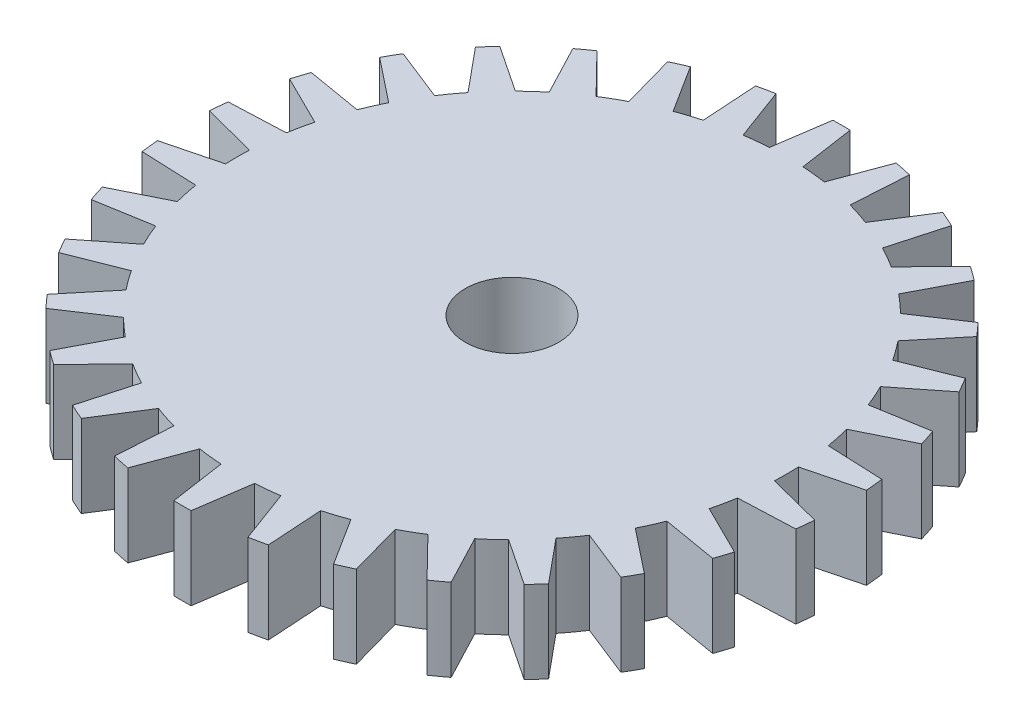
SolidWorks part; units mm, degrees
ref_plane "Front Plane" through (0, 0, 0) normal (0, 0, 1) x (1, 0, 0)
ref_plane "Top Plane" through (0, 0, 0) normal (0, 1, 0) x (1, 0, 0)
ref_plane "Right Plane" through (0, 0, 0) normal (1, 0, 0) x (0, 0, -1)
sketch "Sketch1" plane through (0, 0, 0) normal (0, 1, 0) x (1, 0, 0)
  line L0 (0, 0) -> (0, 12) construction
  line L1 (0, 0) -> (-0.3141, 11.9959) construction
  line L2 (0, 0) -> (-0.6105, 9.9813) construction
  line L3 (0, 0) -> (-1.0453, 9.9452) construction
  line L4 (-0.3141, 11.9959) -> (-0.6105, 9.9813)
  line L5 (0.3141, 11.9959) -> (0.6105, 9.9813)
  line L6 (2.1868, 11.7991) -> (1.4781, 9.8902)
  line L7 (2.8013, 11.6684) -> (2.6724, 9.6363)
  line L8 (4.5922, 11.0866) -> (3.5021, 9.3667)
  line L9 (5.1661, 10.831) -> (4.6175, 8.8701)
  line L10 (6.7969, 9.8895) -> (5.373, 8.4339)
  line L11 (7.3051, 9.5202) -> (6.3608, 7.7162)
  line L12 (8.7045, 8.2603) -> (7.0091, 7.1325)
  line L13 (9.1249, 7.7934) -> (7.8261, 6.2251)
  line L14 (10.2317, 6.27) -> (8.3389, 5.5194)
  line L15 (10.5458, 5.7259) -> (8.9493, 4.462)
  line L16 (11.3117, 4.0057) -> (9.3042, 3.665)
  line L17 (11.5058, 3.4082) -> (9.6815, 2.5038)
  line L18 (11.8973, 1.5663) -> (9.8629, 1.6505)
  line L19 (11.963, 0.9415) -> (9.9905, 0.4362)
  line L20 (11.963, -0.9415) -> (9.9905, -0.4362)
  line L21 (11.8973, -1.5663) -> (9.8629, -1.6505)
  line L22 (11.5058, -3.4082) -> (9.6815, -2.5038)
  line L23 (11.3117, -4.0057) -> (9.3042, -3.665)
  line L24 (10.5458, -5.7259) -> (8.9493, -4.462)
  line L25 (10.2317, -6.27) -> (8.3389, -5.5194)
  line L26 (9.1249, -7.7934) -> (7.8261, -6.2251)
  line L27 (8.7045, -8.2603) -> (7.0091, -7.1325)
  line L28 (7.3051, -9.5202) -> (6.3608, -7.7162)
  line L29 (6.7969, -9.8895) -> (5.373, -8.4339)
  line L30 (5.1661, -10.831) -> (4.6175, -8.8701)
  line L31 (4.5922, -11.0866) -> (3.5021, -9.3667)
  line L32 (2.8013, -11.6684) -> (2.6724, -9.6363)
  line L33 (2.1868, -11.7991) -> (1.4781, -9.8902)
  line L34 (0.3141, -11.9959) -> (0.6105, -9.9813)
  line L35 (-0.3141, -11.9959) -> (-0.6105, -9.9813)
  line L36 (-2.1868, -11.7991) -> (-1.4781, -9.8902)
  line L37 (-2.8013, -11.6684) -> (-2.6724, -9.6363)
  line L38 (-4.5922, -11.0866) -> (-3.5021, -9.3667)
  line L39 (-5.1661, -10.831) -> (-4.6175, -8.8701)
  line L40 (-6.7969, -9.8895) -> (-5.373, -8.4339)
  line L41 (-7.3051, -9.5202) -> (-6.3608, -7.7162)
  line L42 (-8.7045, -8.2603) -> (-7.0091, -7.1325)
  line L43 (-9.1249, -7.7934) -> (-7.8261, -6.2251)
  line L44 (-10.2317, -6.27) -> (-8.3389, -5.5194)
  line L45 (-10.5458, -5.7259) -> (-8.9493, -4.462)
  line L46 (-11.3117, -4.0057) -> (-9.3042, -3.665)
  line L47 (-11.5058, -3.4082) -> (-9.6815, -2.5038)
  line L48 (-11.8973, -1.5663) -> (-9.8629, -1.6505)
  line L49 (-11.963, -0.9415) -> (-9.9905, -0.4362)
  line L50 (-11.963, 0.9415) -> (-9.9905, 0.4362)
  line L51 (-11.8973, 1.5663) -> (-9.8629, 1.6505)
  line L52 (-11.5058, 3.4082) -> (-9.6815, 2.5038)
  line L53 (-11.3117, 4.0057) -> (-9.3042, 3.665)
  line L54 (-10.5458, 5.7259) -> (-8.9493, 4.462)
  line L55 (-10.2317, 6.27) -> (-8.3389, 5.5194)
  line L56 (-9.1249, 7.7934) -> (-7.8261, 6.2251)
  line L57 (-8.7045, 8.2603) -> (-7.0091, 7.1325)
  line L58 (-7.3051, 9.5202) -> (-6.3608, 7.7162)
  line L59 (-6.7969, 9.8895) -> (-5.373, 8.4339)
  line L60 (-5.1661, 10.831) -> (-4.6175, 8.8701)
  line L61 (-4.5922, 11.0866) -> (-3.5021, 9.3667)
  line L62 (-2.8013, 11.6684) -> (-2.6724, 9.6363)
  line L63 (-2.1868, 11.7991) -> (-1.4781, 9.8902)
  arc A0 (0.3141, 11.9959) -> (-0.3141, 11.9959) centre (0, 0) ccw
  arc A1 (-0.6105, 9.9813) -> (-1.0453, 9.9452) centre (0, 0) ccw
  arc A2 (0.6105, 9.9813) -> (1.0453, 9.9452) centre (0, 0) cw
  arc A4 (2.8013, 11.6684) -> (2.1868, 11.7991) centre (0, 0) ccw
  arc A5 (1.4781, 9.8902) -> (1.0453, 9.9452) centre (0, 0) ccw
  arc A6 (2.6724, 9.6363) -> (3.0902, 9.5106) centre (0, 0) cw
  arc A7 (5.1661, 10.831) -> (4.5922, 11.0866) centre (0, 0) ccw
  arc A8 (3.5021, 9.3667) -> (3.0902, 9.5106) centre (0, 0) ccw
  arc A9 (4.6175, 8.8701) -> (5, 8.6603) centre (0, 0) cw
  arc A10 (7.3051, 9.5202) -> (6.7969, 9.8895) centre (0, 0) ccw
  arc A11 (5.373, 8.4339) -> (5, 8.6603) centre (0, 0) ccw
  arc A12 (6.3608, 7.7162) -> (6.6913, 7.4314) centre (0, 0) cw
  arc A13 (9.1249, 7.7934) -> (8.7045, 8.2603) centre (0, 0) ccw
  arc A14 (7.0091, 7.1325) -> (6.6913, 7.4314) centre (0, 0) ccw
  arc A15 (7.8261, 6.2251) -> (8.0902, 5.8779) centre (0, 0) cw
  arc A16 (10.5458, 5.7259) -> (10.2317, 6.27) centre (0, 0) ccw
  arc A17 (8.3389, 5.5194) -> (8.0902, 5.8779) centre (0, 0) ccw
  arc A18 (8.9493, 4.462) -> (9.1355, 4.0674) centre (0, 0) cw
  arc A19 (11.5058, 3.4082) -> (11.3117, 4.0057) centre (0, 0) ccw
  arc A20 (9.3042, 3.665) -> (9.1355, 4.0674) centre (0, 0) ccw
  arc A21 (9.6815, 2.5038) -> (9.7815, 2.0791) centre (0, 0) cw
  arc A22 (11.963, 0.9415) -> (11.8973, 1.5663) centre (0, 0) ccw
  arc A23 (9.8629, 1.6505) -> (9.7815, 2.0791) centre (0, 0) ccw
  arc A24 (9.9905, 0.4362) -> (10, 0) centre (0, 0) cw
  arc A25 (11.8973, -1.5663) -> (11.963, -0.9415) centre (0, 0) ccw
  arc A26 (9.9905, -0.4362) -> (10, 0) centre (0, 0) ccw
  arc A27 (9.8629, -1.6505) -> (9.7815, -2.0791) centre (0, 0) cw
  arc A28 (11.3117, -4.0057) -> (11.5058, -3.4082) centre (0, 0) ccw
  arc A29 (9.6815, -2.5038) -> (9.7815, -2.0791) centre (0, 0) ccw
  arc A30 (9.3042, -3.665) -> (9.1355, -4.0674) centre (0, 0) cw
  arc A31 (10.2317, -6.27) -> (10.5458, -5.7259) centre (0, 0) ccw
  arc A32 (8.9493, -4.462) -> (9.1355, -4.0674) centre (0, 0) ccw
  arc A33 (8.3389, -5.5194) -> (8.0902, -5.8779) centre (0, 0) cw
  arc A34 (8.7045, -8.2603) -> (9.1249, -7.7934) centre (0, 0) ccw
  arc A35 (7.8261, -6.2251) -> (8.0902, -5.8779) centre (0, 0) ccw
  arc A36 (7.0091, -7.1325) -> (6.6913, -7.4314) centre (0, 0) cw
  arc A37 (6.7969, -9.8895) -> (7.3051, -9.5202) centre (0, 0) ccw
  arc A38 (6.3608, -7.7162) -> (6.6913, -7.4314) centre (0, 0) ccw
  arc A39 (5.373, -8.4339) -> (5, -8.6603) centre (0, 0) cw
  arc A40 (4.5922, -11.0866) -> (5.1661, -10.831) centre (0, 0) ccw
  arc A41 (4.6175, -8.8701) -> (5, -8.6603) centre (0, 0) ccw
  arc A42 (3.5021, -9.3667) -> (3.0902, -9.5106) centre (0, 0) cw
  arc A43 (2.1868, -11.7991) -> (2.8013, -11.6684) centre (0, 0) ccw
  arc A44 (2.6724, -9.6363) -> (3.0902, -9.5106) centre (0, 0) ccw
  arc A45 (1.4781, -9.8902) -> (1.0453, -9.9452) centre (0, 0) cw
  arc A46 (-0.3141, -11.9959) -> (0.3141, -11.9959) centre (0, 0) ccw
  arc A47 (0.6105, -9.9813) -> (1.0453, -9.9452) centre (0, 0) ccw
  arc A48 (-0.6105, -9.9813) -> (-1.0453, -9.9452) centre (0, 0) cw
  arc A49 (-2.8013, -11.6684) -> (-2.1868, -11.7991) centre (0, 0) ccw
  arc A50 (-1.4781, -9.8902) -> (-1.0453, -9.9452) centre (0, 0) ccw
  arc A51 (-2.6724, -9.6363) -> (-3.0902, -9.5106) centre (0, 0) cw
  arc A52 (-5.1661, -10.831) -> (-4.5922, -11.0866) centre (0, 0) ccw
  arc A53 (-3.5021, -9.3667) -> (-3.0902, -9.5106) centre (0, 0) ccw
  arc A54 (-4.6175, -8.8701) -> (-5, -8.6603) centre (0, 0) cw
  arc A55 (-7.3051, -9.5202) -> (-6.7969, -9.8895) centre (0, 0) ccw
  arc A56 (-5.373, -8.4339) -> (-5, -8.6603) centre (0, 0) ccw
  arc A57 (-6.3608, -7.7162) -> (-6.6913, -7.4314) centre (0, 0) cw
  arc A58 (-9.1249, -7.7934) -> (-8.7045, -8.2603) centre (0, 0) ccw
  arc A59 (-7.0091, -7.1325) -> (-6.6913, -7.4314) centre (0, 0) ccw
  arc A60 (-7.8261, -6.2251) -> (-8.0902, -5.8779) centre (0, 0) cw
  arc A61 (-10.5458, -5.7259) -> (-10.2317, -6.27) centre (0, 0) ccw
  arc A62 (-8.3389, -5.5194) -> (-8.0902, -5.8779) centre (0, 0) ccw
  arc A63 (-8.9493, -4.462) -> (-9.1355, -4.0674) centre (0, 0) cw
  arc A64 (-11.5058, -3.4082) -> (-11.3117, -4.0057) centre (0, 0) ccw
  arc A65 (-9.3042, -3.665) -> (-9.1355, -4.0674) centre (0, 0) ccw
  arc A66 (-9.6815, -2.5038) -> (-9.7815, -2.0791) centre (0, 0) cw
  arc A67 (-11.963, -0.9415) -> (-11.8973, -1.5663) centre (0, 0) ccw
  arc A68 (-9.8629, -1.6505) -> (-9.7815, -2.0791) centre (0, 0) ccw
  arc A69 (-9.9905, -0.4362) -> (-10, 0) centre (0, 0) cw
  arc A70 (-11.8973, 1.5663) -> (-11.963, 0.9415) centre (0, 0) ccw
  arc A71 (-9.9905, 0.4362) -> (-10, 0) centre (0, 0) ccw
  arc A72 (-9.8629, 1.6505) -> (-9.7815, 2.0791) centre (0, 0) cw
  arc A73 (-11.3117, 4.0057) -> (-11.5058, 3.4082) centre (0, 0) ccw
  arc A74 (-9.6815, 2.5038) -> (-9.7815, 2.0791) centre (0, 0) ccw
  arc A75 (-9.3042, 3.665) -> (-9.1355, 4.0674) centre (0, 0) cw
  arc A76 (-10.2317, 6.27) -> (-10.5458, 5.7259) centre (0, 0) ccw
  arc A77 (-8.9493, 4.462) -> (-9.1355, 4.0674) centre (0, 0) ccw
  arc A78 (-8.3389, 5.5194) -> (-8.0902, 5.8779) centre (0, 0) cw
  arc A79 (-8.7045, 8.2603) -> (-9.1249, 7.7934) centre (0, 0) ccw
  arc A80 (-7.8261, 6.2251) -> (-8.0902, 5.8779) centre (0, 0) ccw
  arc A81 (-7.0091, 7.1325) -> (-6.6913, 7.4314) centre (0, 0) cw
  arc A82 (-6.7969, 9.8895) -> (-7.3051, 9.5202) centre (0, 0) ccw
  arc A83 (-6.3608, 7.7162) -> (-6.6913, 7.4314) centre (0, 0) ccw
  arc A84 (-5.373, 8.4339) -> (-5, 8.6603) centre (0, 0) cw
  arc A85 (-4.5922, 11.0866) -> (-5.1661, 10.831) centre (0, 0) ccw
  arc A86 (-4.6175, 8.8701) -> (-5, 8.6603) centre (0, 0) ccw
  arc A87 (-3.5021, 9.3667) -> (-3.0902, 9.5106) centre (0, 0) cw
  arc A88 (-2.1868, 11.7991) -> (-2.8013, 11.6684) centre (0, 0) ccw
  arc A89 (-2.6724, 9.6363) -> (-3.0902, 9.5106) centre (0, 0) ccw
  arc A90 (-1.4781, 9.8902) -> (-1.0453, 9.9452) centre (0, 0) cw
  point P14 (0, 0)
  point P185 (0, 0)
  dimension "D1" = 1.5
  dimension "D2" = 2
  dimension "D3" = 2.5
  dimension "D4" = 30
  dimension "D5" = 10
extrude "Boss-Extrude1" add sketch "Sketch1" along normal blind 3
sketch "Sketch2" plane through (0, 3, 0) normal (0, 1, 0) x (1, 0, 0)
  circle A0 centre (0, 0) radius 1.7
  dimension "D1" = 3.4
extrude "Cut-Extrude1" cut sketch "Sketch2" against normal through all
